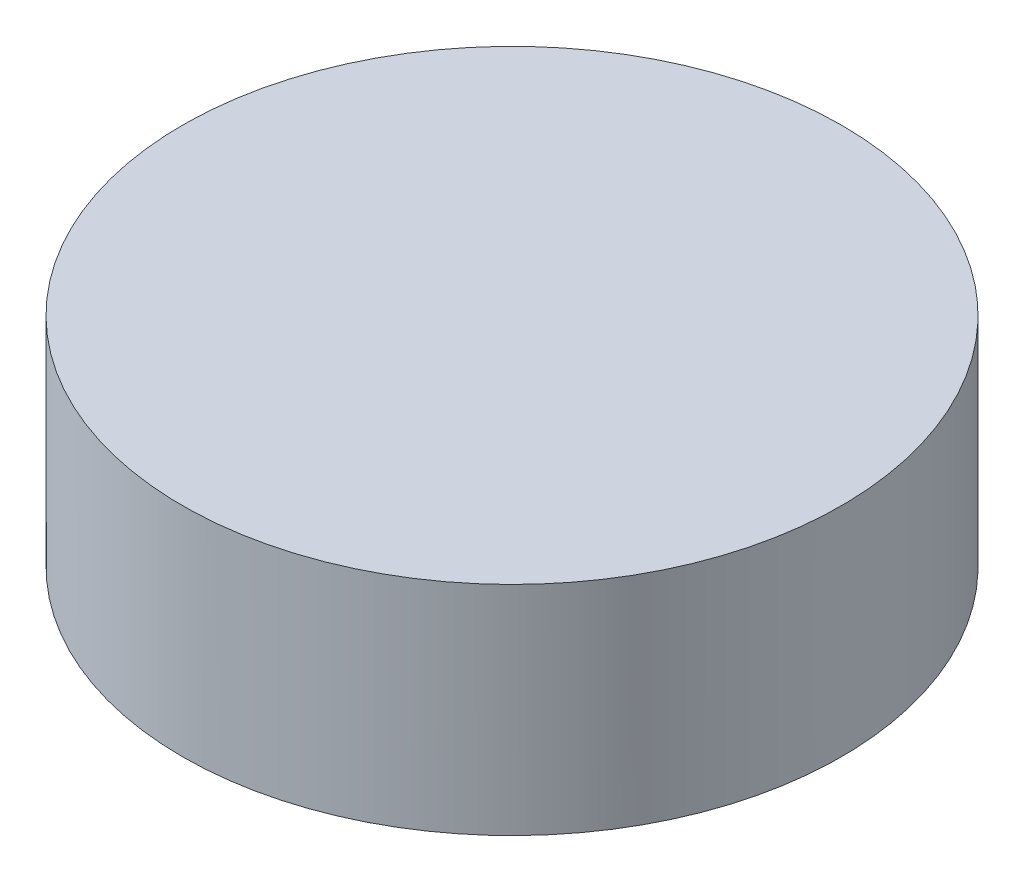
SolidWorks part; units mm, degrees
ref_plane "Спереди" through (0, 0, 0) normal (0, 0, 1) x (1, 0, 0)
ref_plane "Сверху" through (0, 0, 0) normal (0, 1, 0) x (1, 0, 0)
ref_plane "Справа" through (0, 0, 0) normal (1, 0, 0) x (0, 0, -1)
sketch "Эскиз1" plane through (0, 0, 0) normal (0, 1, 0) x (1, 0, 0)
  circle A0 centre (0, 0) radius 15
extrude "Вытянуть1" add sketch "Эскиз1" along normal up to surface (9.9 mm away)
